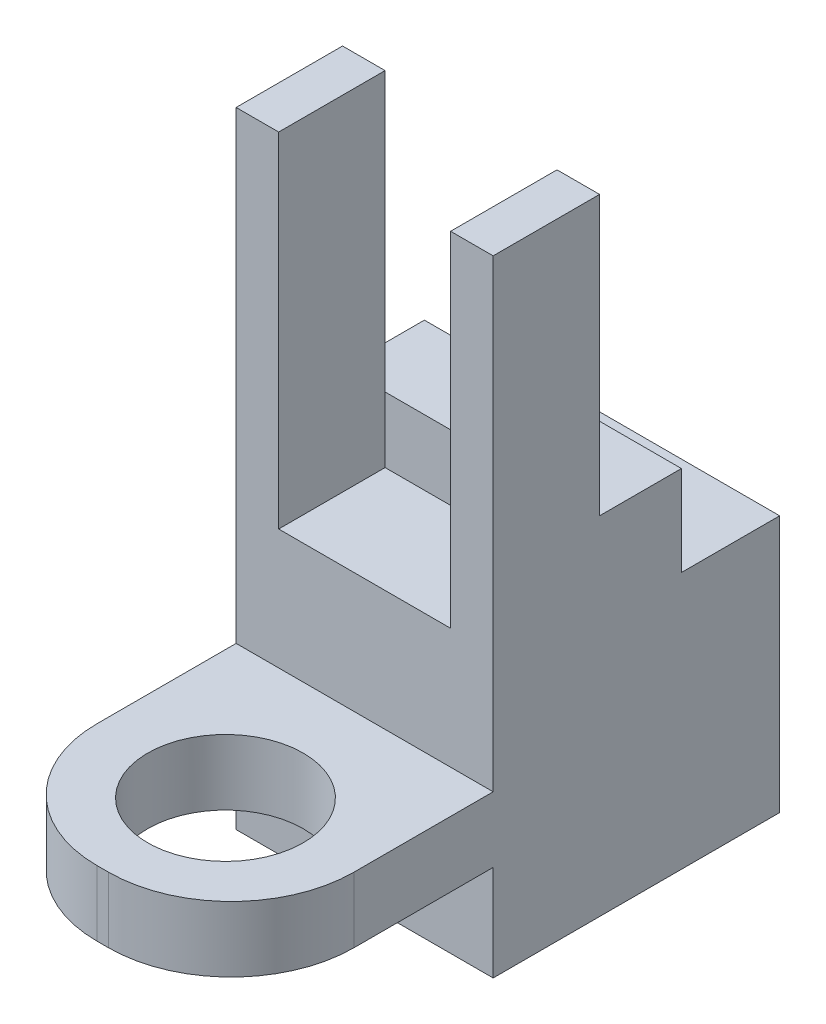
SolidWorks part; units mm, degrees
ref_plane "Front Plane" through (0, 0, 0) normal (0, 0, 1) x (1, 0, 0)
ref_plane "Top Plane" through (0, 0, 0) normal (0, 1, 0) x (1, 0, 0)
ref_plane "Right Plane" through (0, 0, 0) normal (1, 0, 0) x (0, 0, -1)
sketch "Sketch4" plane through (0, 0, 0) normal (0, 0, 1) x (1, 0, 0)
  line L0 (0, 82.063) -> (0, -112.4411) construction
  line L1 (-144.2959, 0) -> (145.5617, 0) construction
  line L2 (-12.7, 12.7) -> (-12.7, -12.7)
  line L3 (-15.7, 15.7) -> (15.7, 15.7)
  line L4 (-15.7, 15.7) -> (-15.7, -15.7)
  line L5 (-15.7, -15.7) -> (15.7, -15.7)
  line L6 (15.7, 15.7) -> (15.7, -15.7)
  line L7 (-12.7, -12.7) -> (12.7, -12.7)
  line L8 (12.7, 12.7) -> (12.7, -12.7)
  line L9 (-12.7, 12.7) -> (12.7, 12.7)
  dimension "D2" = 12.7
  dimension "D3" = 12.7
  dimension "D4" = 12.7
  dimension "D5" = 12.7
  dimension "D1" = 3
extrude "Boss-Extrude3" add sketch "Sketch4" along normal blind 30
sketch "Sketch5" plane through (0, 0, 30) normal (0, 0, 1) x (1, 0, 0)
  line L0 (-15.7, 15.7) -> (15.7, 15.7)
  line L1 (15.7, 15.7) -> (15.7, -15.7)
  line L2 (15.7, -15.7) -> (-15.7, -15.7)
  line L3 (-15.7, -15.7) -> (-15.7, 15.7)
extrude "Boss-Extrude4" add sketch "Sketch5" along normal blind 5
sketch "Sketch6" plane through (0, 0, 35) normal (0, 0, 1) x (1, 0, 0)
  line L0 (-14.6567, 0) -> (15.7, 0) construction
  line L1 (15.7, -15.7) -> (15.7, 15.7) construction
  line L2 (-15.7, 4) -> (15.7, 4)
  line L3 (-15.7, 15.7) -> (-15.7, -15.7) construction
  line L4 (15.7, 4) -> (15.7, -4)
  line L5 (15.7, -4) -> (-15.7, -4)
  line L6 (-15.7, -4) -> (-15.7, 4)
  dimension "D1" = 4
  dimension "D2" = 4
extrude "Boss-Extrude5" add sketch "Sketch6" along normal blind 5
sketch "Sketch7" plane through (0, -4, 0) normal (0, -1, 0) x (1, 0, 0)
  line L0 (-15.7, 40) -> (-15.7, 52)
  line L1 (-0.7, 67) -> (0.7, 67)
  line L2 (15.7, 52) -> (15.7, 40)
  line L3 (-15.7, 40) -> (15.7, 40) construction
  line L4 (15.7, 40) -> (-15.7, 40)
  line L5 (0, 0) -> (0, 92.3619) construction
  arc A0 (0.7, 67) -> (15.7, 52) centre (0.7, 52) cw
  arc A1 (-15.7, 52) -> (-0.7, 67) centre (-0.7, 52) cw
  point P9 (15.7, 67)
  point P12 (-15.7, 67)
  dimension "D3" = 15
  dimension "D1" = 27
  dimension "D2" = 31.4
extrude "Boss-Extrude6" add sketch "Sketch7" against normal blind 8
sketch "Sketch8" plane through (0, -4, 0) normal (0, -1, 0) x (1, 0, 0)
  line L0 (0, 67.4318) -> (0, -5.9603) construction
  line L1 (0.7, 67) -> (-0.7, 67) construction
  circle A0 centre (0, 52) radius 9.5
  dimension "D1" = 15
extrude "Boss-Extrude7" add sketch "Sketch8" along normal blind 8
mirror "Mirror1" about plane through (0, 0, 0) normal (0, 1, 0) of "Boss-Extrude7"
sketch "Sketch9" plane through (0, 15.7, 0) normal (0, 1, 0) x (1, 0, 0)
  line L1 (-15.7, -32) -> (15.7, -32)
  line L2 (-15.7, -35) -> (-15.7, 0) construction
  line L3 (15.7, -35) -> (15.7, 0) construction
  line L4 (0, 15.8647) -> (0, -78.6922) construction
  line L5 (0, -52) -> (31.7707, -52) construction
  line L6 (31.7707, -52) -> (-30.9902, -52) construction
  line L7 (-15.7, -32) -> (-15.7, -22)
  line L8 (-15.7, -22) -> (15.7, -22)
  line L9 (15.7, -22) -> (15.7, -32)
  dimension "D1" = 20
  dimension "D2" = 10
extrude "Boss-Extrude8" add sketch "Sketch9" along normal blind 5
sketch "Sketch10" plane through (0, 15.7, 0) normal (0, 1, 0) x (1, 0, 0)
  line L0 (-15.7, -22) -> (-15.7, -12)
  line L1 (-15.7, -22) -> (-15.7, 0) construction
  line L2 (-15.7, -12) -> (15.7, -12)
  line L3 (15.7, -22) -> (15.7, 0) construction
  line L4 (15.7, -12) -> (15.7, -22)
  line L5 (15.7, -22) -> (-15.7, -22)
  dimension "D1" = 10
extrude "Boss-Extrude9" add sketch "Sketch10" along normal blind 11
sketch "Sketch11" plane through (0, 20.7, 0) normal (0, 1, 0) x (1, 0, 0)
  line L0 (-15.7, -22) -> (-10.5, -22)
  line L1 (15.7, -22) -> (-15.7, -22) construction
  line L2 (-10.5, -22) -> (-10.5, -32)
  line L3 (-15.7, -32) -> (15.7, -32) construction
  line L4 (-10.5, -32) -> (-15.7, -32)
  line L5 (-15.7, -32) -> (-15.7, -22)
  line L6 (10.5, -22) -> (10.5, -32)
  line L7 (-15.7, -22) -> (15.7, -22) construction
  line L8 (-15.7, -32) -> (15.7, -32) construction
  line L9 (10.5, -32) -> (15.7, -32)
  line L10 (15.7, -32) -> (15.7, -22)
  line L11 (15.7, -32) -> (15.7, -22) construction
  line L12 (15.7, -22) -> (10.5, -22)
  dimension "D1" = 5.2
  dimension "D2" = 5.2
extrude "Boss-Extrude10" add sketch "Sketch11" along normal blind 40
sketch "Sketch12" plane through (0, 0, 32) normal (0, 0, 1) x (1, 0, 0)
  line L0 (-15.7, 60.7) -> (-10.5, 60.7)
  line L1 (-10.5, 60.7) -> (-10.5, 20.7)
  line L2 (-10.5, 20.7) -> (10.5, 20.7)
  line L3 (10.5, 20.7) -> (10.5, 60.7)
  line L4 (10.5, 60.7) -> (15.7, 60.7)
  line L5 (15.7, 60.7) -> (15.7, 15.7)
  line L6 (15.7, 15.7) -> (-15.7, 15.7)
  line L7 (-15.7, 15.7) -> (-15.7, 60.7)
extrude "Boss-Extrude11" add sketch "Sketch12" along normal blind 3
extrude "Cut-Extrude1" cut sketch "Sketch8<2>" against normal blind 24 from offset 8
sketch "Sketch8<2>" plane through (0, -4, 0) normal (0, -1, 0) x (1, 0, 0) same geometry as "Sketch8"
sketch "Sketch14" plane through (0, 20.7, 0) normal (0, 1, 0) x (1, 0, 0)
  line L0 (-10.5, -22) -> (10.5, -22)
  line L1 (10.5, -22) -> (10.5, -35)
  line L2 (10.5, -35) -> (-10.5, -35)
  line L3 (-10.5, -35) -> (-10.5, -22)
extrude "Cut-Extrude2" cut sketch "Sketch14" against normal blind 2
